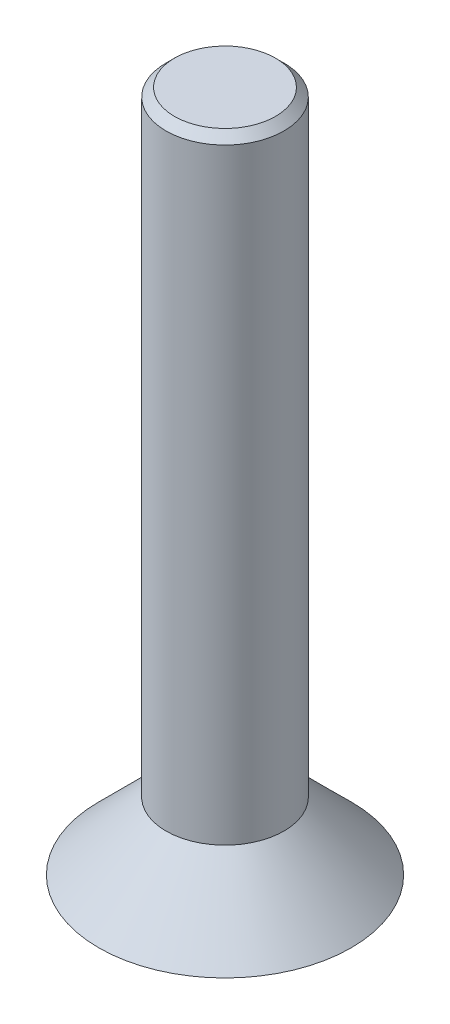
SolidWorks part; units mm, degrees
material "铸造合金钢"
ref_plane "前视基准面" through (0, 0, 0) normal (0, 0, 1) x (1, 0, 0)
ref_plane "上视基准面" through (0, 0, 0) normal (0, 1, 0) x (1, 0, 0)
ref_plane "右视基准面" through (0, 0, 0) normal (1, 0, 0) x (0, 0, -1)
sketch "草图1" plane through (0, 0, 0) normal (0, 1, 0) x (1, 0, 0)
  line L1 (0, -1.1547) -> (1, -0.5774)
  line L2 (1, -0.5774) -> (1, 0.5774)
  line L3 (1, 0.5774) -> (0, 1.1547)
  line L4 (0, 1.1547) -> (-1, 0.5774)
  line L5 (-1, 0.5774) -> (-1, -0.5774)
  line L6 (-1, -0.5774) -> (0, -1.1547)
  circle A0 centre (0, 0) radius 3
  circle A1 centre (0, 0) radius 1 construction
  dimension "D1" = 6
  dimension "D2" = 2
extrude "凸台-拉伸1" add sketch "草图1" along normal blind 1.6
chamfer "倒角1" distance 1.6 angle 45 1 edges at (0, 1.6, 3)
sketch "草图2" plane through (0, 1.6, 0) normal (0, 1, 0) x (1, 0, 0)
  circle A0 centre (0, 0) radius 1.4
  dimension "D1" = 2.8
extrude "凸台-拉伸2" add sketch "草图2" along normal blind 14.6
chamfer "倒角2" distance 0.2 angle 45 1 edges at (0, 16.2, 1.4)
